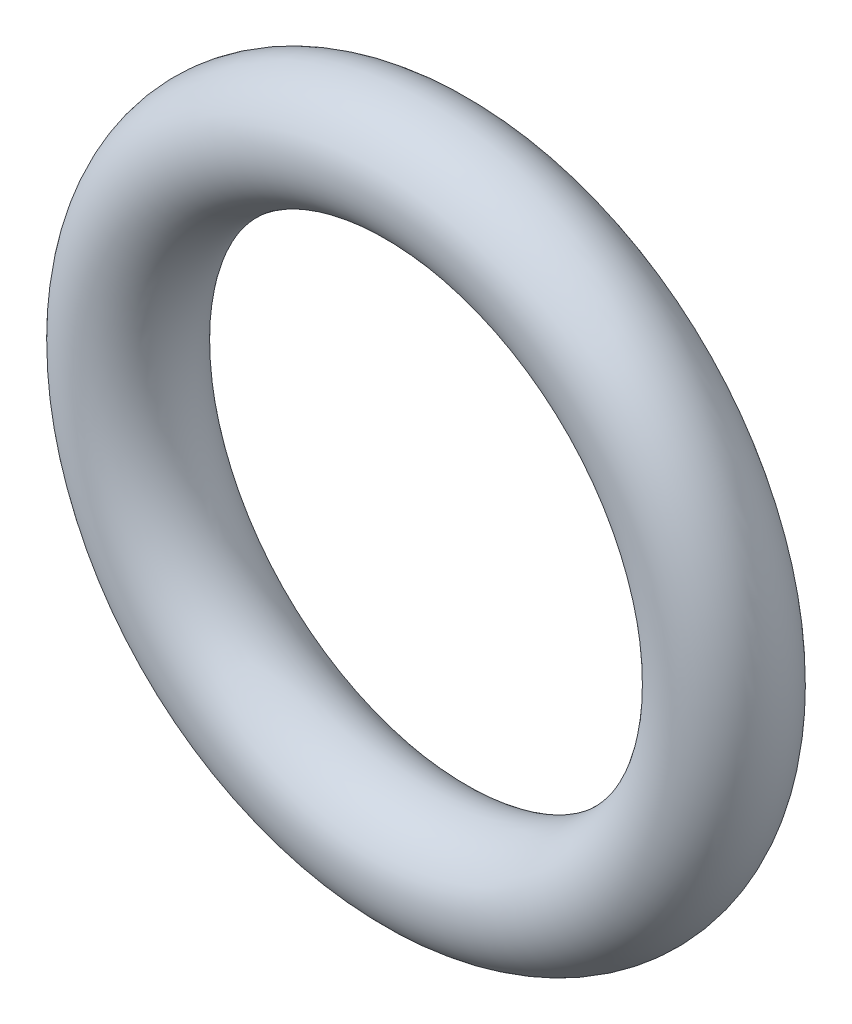
SolidWorks part; units mm, degrees
ref_plane "Front" through (0, 0, 0) normal (0, 0, 1) x (1, 0, 0)
ref_plane "Top" through (0, 0, 0) normal (0, 1, 0) x (1, 0, 0)
ref_plane "Right" through (0, 0, 0) normal (1, 0, 0) x (0, 0, -1)
sketch "Sketch1" plane through (0, 0, 0) normal (0, 0, 1) x (1, 0, 0)
  circle A0 centre (0, 0) radius 3.75
  dimension "d1" = 7.5
sketch "Sketch2" plane through (0, 0, 0) normal (0, 1, 0) x (1, 0, 0)
  circle A0 centre (-4.65, 0) radius 0.9
  point P2 (-3.75, 0)
  dimension "d2" = 1.8
sweep "Sweep1" add profiles "Sketch2" path "Sketch1"
ref_axis "Axis1" through (0, 0, -5.0798) along (0, 0, 1)
